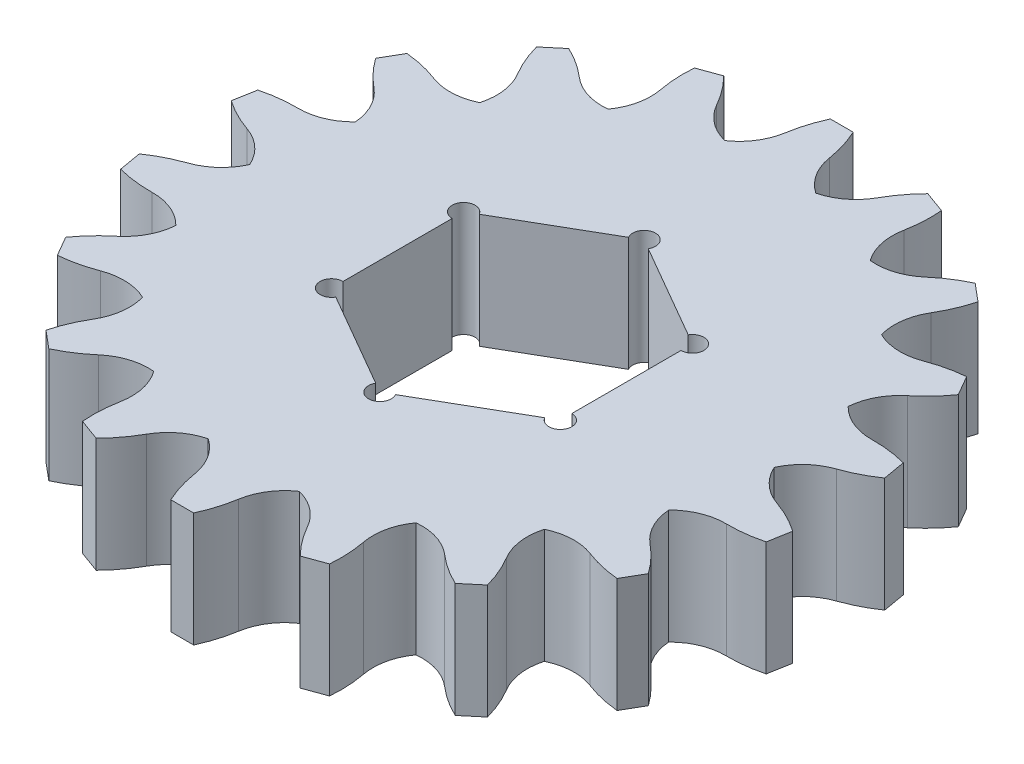
SolidWorks part; units mm, degrees
ref_plane "Front Plane" through (0, 0, 0) normal (0, 0, 1) x (1, 0, 0)
ref_plane "Top Plane" through (0, 0, 0) normal (0, 1, 0) x (1, 0, 0)
ref_plane "Right Plane" through (0, 0, 0) normal (1, 0, 0) x (0, 0, -1)
sketch "Sketch1" plane through (0, 0, 0) normal (0, 1, 0) x (1, 0, 0)
  line L2 (0.5, 14.4154) -> (-0.5, 14.4154)
  line L3 (-1, 11.4154) -> (1, 11.4154)
  line L4 (0, 14.4154) -> (0, 11.4154)
  line L6 (0, -5) -> (0, 5)
  line L8 (0, 12.9154) -> (0.9583, 12.9154)
  line L9 (0, 12.9154) -> (-0.9583, 12.9154)
  line L10 (-2, 11.2833) -> (2, 11.2833)
  line L11 (0, 5.7735) -> (-5, 2.8868)
  line L12 (-5, 2.8868) -> (-5, -2.8868)
  line L13 (-5, -2.8868) -> (0, -5.7735)
  line L14 (0, -5.7735) -> (5, -2.8868)
  line L15 (5, -2.8868) -> (5, 2.8868)
  line L16 (5, 2.8868) -> (0, 5.7735)
  circle A0 centre (0, 0) radius 11.4592
  arc A1 (-1, 11.4154) -> (-0.5, 14.4154) centre (4.6965, 12.0077) cw
  arc A2 (0.5, 14.4154) -> (1, 11.4154) centre (-4.6965, 12.0077) cw
  circle A3 centre (0, 0) radius 5
  arc A4 (-0.9583, 12.9154) -> (-2, 11.2833) centre (-3.3625, 13.3014) cw
  arc A5 (0.9583, 12.9154) -> (2, 11.2833) centre (3.3625, 13.3014) ccw
  circle A6 centre (0, 0) radius 5 construction
  circle A7 centre (0, 5.7735) radius 0.5
  circle A8 centre (5, 2.8868) radius 0.5
  circle A9 centre (5, -2.8868) radius 0.5
  circle A10 centre (0, -5.7735) radius 0.5
  circle A11 centre (-5, -2.8868) radius 0.5
  circle A12 centre (-5, 2.8868) radius 0.5
  dimension "D4" = 5.7272
  dimension "D5" = 22.9183
  dimension "D6" = 10
  dimension "D7" = 1
  dimension "D1" = 3
  dimension "D2" = 2
  dimension "D3" = 1
  dimension "D8" = 4
  dimension "D9" = 6
extrude "Boss-Extrude1" add sketch "Sketch1" along normal blind 5 contours A1 L2 A2 L3 | L10 A5 L8 L9 A4
sketch "Sketch4" plane through (0, 0, 0) normal (1, 0, 0) x (0, 0, -1)
  line L0 (0, 0) -> (0, 7.6311)
pattern_circular "CirPattern2" count 18 over 360 about axis through (0, 0, 0) along (0, 1, 0) of "Boss-Extrude1" reverse direction yes
extrude "Boss-Extrude3" add sketch "Sketch1<5>" along normal blind 5 contours L10 A0 A3 region at (8.5341, 0, -7.1544)
sketch "Sketch1<5>" plane through (0, 0, 0) normal (0, 1, 0) x (1, 0, 0) same geometry as "Sketch1"
equation "\"teeth\" = 18'num of teeth in gear"
equation "\"gearRadius\"= \"teeth\" * 4 / ( 2 * Pi )"
equation "\"D5@Sketch1\"=\"gearRadius\"*2"
equation "\"D1@CirPattern2\"=\"teeth\""
equation "\"thick\"= 5"
equation "\"D1@Boss-Extrude1\"=\"thick\""
equation "\"D1@Boss-Extrude3\"=\"thick\""
equation "\"innerDia\"= 10"
equation "\"D6@Sketch1\"=\"innerDia\""
